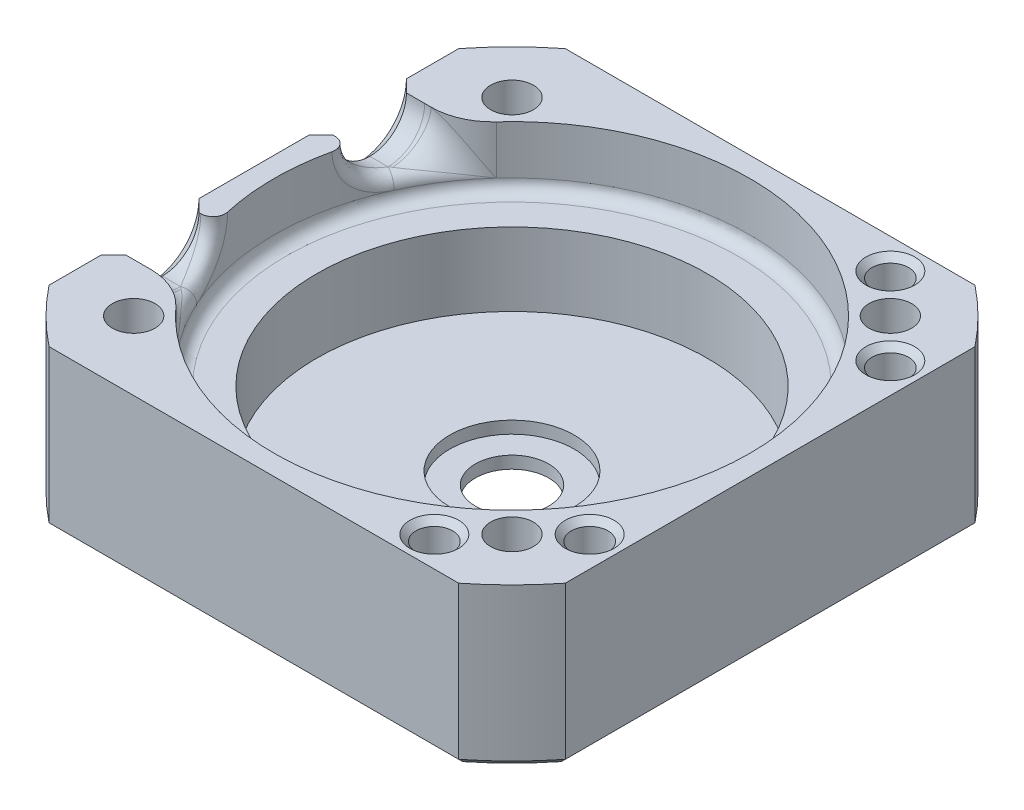
SolidWorks part; units mm, degrees
ref_plane "Front Plane" through (0, 0, 0) normal (0, 0, 1) x (1, 0, 0)
ref_plane "Top Plane" through (0, 0, 0) normal (0, 1, 0) x (1, 0, 0)
ref_plane "Right Plane" through (0, 0, 0) normal (1, 0, 0) x (0, 0, -1)
sketch "Sketch2" plane through (0, 0, 0) normal (0, 1, 0) x (1, 0, 0)
  line L1 (-21.15, 21.15) -> (21.15, 21.15)
  line L2 (-21.15, 21.15) -> (-21.15, -21.15)
  line L3 (-21.15, -21.15) -> (21.15, -21.15)
  line L4 (21.15, 21.15) -> (21.15, -21.15)
  line L5 (-21.15, 21.15) -> (21.15, -21.15) construction
  line L6 (-21.15, -21.15) -> (21.15, 21.15) construction
  point P0 (0, 0)
  dimension "D1" = 42.3
extrude "Boss-Extrude1" add sketch "Sketch2" along normal blind 13
sketch "Sketch3" plane through (0, 13, 0) normal (0, 1, 0) x (1, 0, 0)
  circle A0 centre (0, 0) radius 3
  dimension "D1" = 6
extrude "Cut-Extrude1" cut sketch "Sketch3" against normal through all
sketch "Sketch4" plane through (0, 13, 0) normal (0, 1, 0) x (1, 0, 0)
  line L1 (-15.5, 15.5) -> (15.5, 15.5) construction
  line L2 (-15.5, 15.5) -> (-15.5, -15.5) construction
  line L3 (-15.5, -15.5) -> (15.5, -15.5) construction
  line L4 (15.5, 15.5) -> (15.5, -15.5) construction
  line L5 (-15.5, 15.5) -> (15.5, -15.5) construction
  line L6 (-15.5, -15.5) -> (15.5, 15.5) construction
  circle A0 centre (-15.5, 15.5) radius 1.75
  circle A1 centre (15.5, 15.5) radius 1.75
  circle A2 centre (15.5, -15.5) radius 1.75
  circle A3 centre (-15.5, -15.5) radius 1.75
  point P0 (0, 0)
  point P16 (0, 0)
  dimension "D3" = 3.5
  dimension "D1" = 31
  dimension "D2" = 31
  dimension "D4" = 4
extrude "Cut-Extrude2" cut sketch "Sketch4" against normal through all
sketch "Sketch5" plane through (0, 13, 0) normal (0, 1, 0) x (1, 0, 0)
  circle A0 centre (0, 0) radius 27
  circle A1 centre (0, 0) radius 29.9106
  dimension "D1" = 54
extrude "Cut-Extrude4" cut sketch "Sketch5" against normal through all
sketch "Sketch6" plane through (0, 13, 0) normal (0, 1, 0) x (1, 0, 0)
  line L11 (-15.748, 11.5) -> (-21.15, 11.5)
  line L12 (6.4272, 21.15) -> (21.15, 6.4272) construction
  line L13 (7.3751, 21.15) -> (21.15, 7.3751) construction
  line L14 (16.7833, 21.15) -> (-16.7833, 21.15) construction
  line L15 (21.15, -16.7833) -> (21.15, 16.7833) construction
  line L18 (-21.15, 16.7833) -> (-21.15, -16.7833) construction
  line L24 (-21.15, 11.5) -> (-21.15, 5.5)
  line L25 (-21.15, 5.5) -> (-18.7083, 5.5)
  line L26 (-18.7083, -5.5) -> (-21.15, -5.5)
  line L27 (-21.15, -5.5) -> (-21.15, -11.5)
  line L28 (-21.15, -11.5) -> (-15.748, -11.5)
  line L29 (-21.15, 8.5) -> (-21.15, -8.5) construction
  arc A0 (-15.748, 11.5) -> (-15.748, -11.5) centre (0, 0) cw
  arc A2 (-18.7083, 5.5) -> (-18.7083, -5.5) centre (0, 0) ccw
  circle A3 centre (0, 0) radius 11 construction
  circle A5 centre (15.5, 15.5) radius 1.75 construction
  arc A6 (-15.748, -11.5) -> (-15.748, 11.5) centre (0, 0) ccw
  circle M13 centre (0, 0) radius 3
  line M14 (-16.7833, -21.15) -> (16.7833, -21.15)
  line M20 (-21.15, 16.7833) -> (-21.15, -16.7833)
  dimension "D1" = 6
  dimension "D3" = 19.5
  dimension "D5" = 22
  dimension "D2" = 17
  dimension "D4" = 45
extrude "Cut-Extrude5" cut sketch "Sketch6" against normal offset from surface (11 mm away) 2 contours A2 A0 M14 M20 M13 region at (18.9367, 13, 0) up to face at (-15.5, 0, 17.25)
sketch "Sketch7" plane through (0, 2, 0) normal (0, 1, 0) x (1, 0, 0)
  circle A0 centre (0, 0) radius 5.1
  dimension "D1" = 10.2
extrude "Cut-Extrude6" cut sketch "Sketch7" against normal blind 1
sketch "Sketch8" plane through (0, 2, 0) normal (0, 1, 0) x (1, 0, 0)
  line L6 (-21.15, 5.5) -> (-18.7083, 5.5)
  line L7 (-21.15, 5.5) -> (-18.7083, 5.5)
  line L8 (-18.7083, -5.5) -> (-21.15, -5.5)
  line L9 (-18.7083, -5.5) -> (-21.15, -5.5)
  line L10 (-21.15, -5.5) -> (-21.15, -11.5)
  line L11 (-21.15, -5.5) -> (-21.15, -11.5)
  line L18 (-21.15, -11.5) -> (-15.748, -11.5)
  line L19 (-21.15, -11.5) -> (-15.748, -11.5)
  line L20 (-15.748, 11.5) -> (-21.15, 11.5)
  line L21 (-15.748, 11.5) -> (-21.15, 11.5)
  line L22 (-21.15, 11.5) -> (-21.15, 5.5)
  line L23 (-21.15, 11.5) -> (-21.15, 5.5)
  circle A0 centre (0, 0) radius 16
  arc A3 (-18.7083, 5.5) -> (-18.7083, -5.5) centre (0, 0) ccw
  arc A4 (-15.748, -11.5) -> (-15.748, 11.5) centre (0, 0) ccw
  arc A5 (-18.7083, 5.5) -> (-18.7083, -5.5) centre (0, 0) ccw
  arc A6 (-15.748, -11.5) -> (-15.748, 11.5) centre (0, 0) ccw
  dimension "D1" = 32
  dimension "D2" = 0
extrude "Boss-Extrude2" add sketch "Sketch8" along normal offset from surface (6 mm away) 5 up to face at (-3.2123, 13, 0)
sketch "Sketch9" plane through (0, 13, 0) normal (0, 1, 0) x (1, 0, 0)
  line L0 (12.318, 18.682) -> (18.682, 12.318) construction
  line L1 (-16.7833, -21.15) -> (16.7833, -21.15) construction
  line L2 (-21.15, 0) -> (21.15, 0) construction
  line L3 (-21.15, 5.5) -> (-21.15, -5.5) construction
  line L4 (21.15, -16.7833) -> (21.15, 16.7833) construction
  line L5 (12.318, -18.682) -> (18.682, -12.318) construction
  circle A0 centre (15.5, 15.5) radius 1.75 construction
  circle A1 centre (12.318, 18.682) radius 1.5
  circle A2 centre (18.682, 12.318) radius 1.5
  circle A7 centre (18.682, -12.318) radius 1.5
  circle A8 centre (12.318, -18.682) radius 1.5
  point P2 (15.5, 15.5)
  dimension "D2" = 3
  dimension "D3" = 3
  dimension "D1" = 4.5
  dimension "D4" = 45
extrude "Cut-Extrude7" cut sketch "Sketch9" against normal blind 3
sketch "Sketch10" plane through (0, 8, 0) normal (0, 1, 0) x (1, 0, 0)
  line L0 (-21.15, 5.5) -> (-18.7083, 5.5) construction
  line L2 (-18.7083, -5.5) -> (-21.15, -5.5) construction
  line L3 (-15.748, 11.5) -> (-21.15, 11.5)
  line L4 (-21.15, 11.5) -> (-21.15, 5.5)
  line L5 (-21.15, 5.5) -> (-18.7083, 5.5)
  line L6 (-18.7083, -5.5) -> (-21.15, -5.5)
  line L7 (-21.15, -5.5) -> (-21.15, -11.5)
  line L8 (-21.15, -11.5) -> (-15.748, -11.5)
  arc A0 (-15.748, 11.5) -> (-18.7083, 5.5) centre (0, 0) ccw
  arc A1 (-15.748, -11.5) -> (-18.7083, -5.5) centre (0, 0) cw
extrude "Boss-Extrude3" add sketch "Sketch10" along normal blind 2
chamfer "Chamfer1" distance 1.8 angle 45 4 edges at (15.5, 0, -13.75) (-15.5, 0, -13.75) (-15.5, 0, 17.25) (15.5, 0, 17.25)
chamfer "Chamfer3" distance 0.5 angle 45 4 edges at (12.318, 13, -17.182) (18.682, 13, -10.818) (18.682, 13, 10.818) (12.318, 13, 17.182)
chamfer "Chamfer4" distance 0.5 angle 45 8 edges at (19.0919, 0, 19.0919) (0, 0, 21.15) (-19.0919, 0, 19.0919) (-21.15, 0, 0) (-19.0919, 0, -19.0919) (0, 0, -21.15) (19.0919, 0, -19.0919) (21.15, 0, 0)
fillet "Fillet10" radius 5 2 edges at (-15.748, 11.5, -11.5) (-15.748, 11.5, 11.5)
fillet "Fillet11" radius 3 2 edges at (-19.9291, 10, 5.5) (-19.9291, 10, -5.5)
fillet "Fillet6" radius 1 1 edges at (0, 8, 19.5)
fillet "Fillet9" radius 1 4 edges at (-16.1493, 10, -10.9293) (-16.1493, 10, 10.9293) (-18.5193, 11.1917, 6.1063) (-18.3756, 10.7409, -6.526)
fillet "Fillet8" radius 3 6 edges at (-19.6304, 10, -11.5) (-19.6304, 10, 11.5) (-16.0847, 9.8802, -11.9289) (-17.4814, 10, -11.5398) (-16.0847, 9.8802, 11.9289) (-17.4814, 10, 11.5398)
chamfer "Chamfer5" distance 1 angle 45 4 edges at (-21.15, 10.8787, 10.6213) (-21.15, 10.8787, 6.3787) (-21.15, 10.8787, -6.3787) (-21.15, 10.8787, -10.6213)
